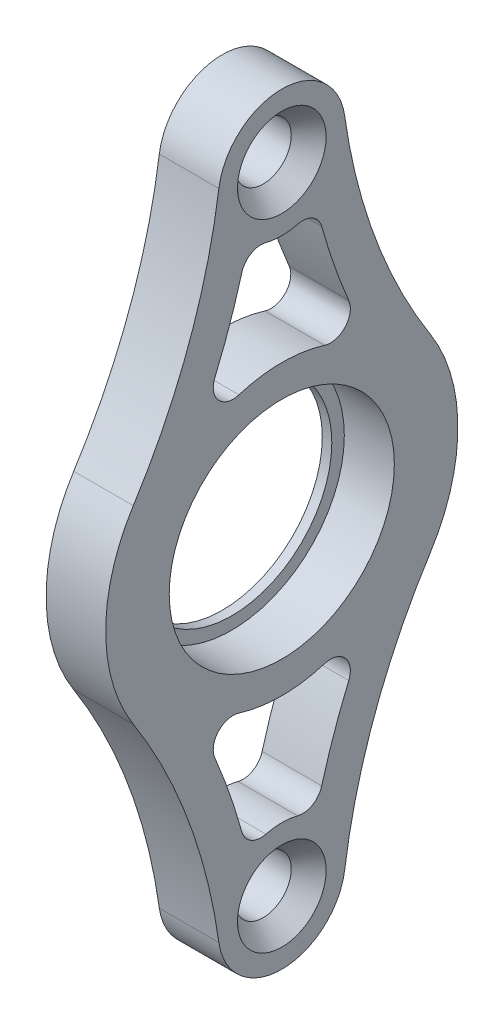
SolidWorks part; units mm, degrees
material "6061-T6 (SS)"
ref_plane "Front Plane" through (0, 0, 0) normal (0, 0, 1) x (1, 0, 0)
ref_plane "Top Plane" through (0, 0, 0) normal (0, 1, 0) x (1, 0, 0)
ref_plane "Right Plane" through (0, 0, 0) normal (1, 0, 0) x (0, 0, -1)
ref_plane "Plane1" through (56.0295, 0, 0) normal (-1, 0, 0) x (0, 0, 1)
sketch "Sketch1" plane through (56.0295, 0, 0) normal (-1, 0, 0) x (0, 0, 1)
  line L0 (-51.1134, 32.5835) -> (-5.0306, 26.107) construction
  line L1 (-23.0873, 0) -> (0, 0) construction
  line L2 (0, 0) -> (0, 25.4) construction
  circle A2 centre (0, -25.4) radius 2.2479
  circle A3 centre (0, 25.4) radius 2.2479
  circle A4 centre (0, 0) radius 9
  circle A5 centre (0, 0) radius 6 construction
  arc A6 (-11.8728, 7.5686) -> (-11.8728, -7.5686) centre (0, 0) ccw
  arc A7 (5.0306, 26.107) -> (-5.0306, 26.107) centre (0, 25.4) ccw
  arc A8 (-5.0306, -26.107) -> (5.0306, -26.107) centre (0, -25.4) ccw
  arc A9 (-5.0306, 26.107) -> (-11.8728, 7.5686) centre (-51.1134, 32.5835) cw
  arc A10 (5.0306, 26.107) -> (11.8728, 7.5686) centre (51.1134, 32.5835) ccw
  arc A11 (5.0306, -26.107) -> (11.8728, -7.5686) centre (51.1134, -32.5835) cw
  arc A12 (-5.0306, -26.107) -> (-11.8728, -7.5686) centre (-51.1134, -32.5835) ccw
  arc A13 (11.8728, -7.5686) -> (11.8728, 7.5686) centre (0, 0) ccw
  circle A14 centre (0, 25.4) radius 2.2479 construction
  circle A15 centre (0, -25.4) radius 2.2479 construction
  dimension "D1" = 18
  dimension "D2" = 12
  dimension "D4" = 10.16
  dimension "D3" = 5.08
  dimension "D5" = 8
extrude "Boss-Extrude1" add sketch "Sketch1" along normal blind 4.7625
sketch "Sketch2" plane through (51.267, 0, 0) normal (-1, 0, 0) x (0, 0, 1)
  arc A0 (-9.1955, 5.8619) -> (-1.8865, 25.6651) centre (-51.1134, 32.5835) ccw
  arc A1 (1.8865, 25.6651) -> (-1.8865, 25.6651) centre (0, 25.4) ccw
  arc A2 (1.8865, 25.6651) -> (9.1955, 5.8619) centre (51.1134, 32.5835) ccw
  arc A3 (9.1955, -5.8619) -> (9.1955, 5.8619) centre (0, 0) ccw
  arc A4 (9.1955, -5.8619) -> (1.8865, -25.6651) centre (51.1134, -32.5835) ccw
  arc A5 (-1.8865, -25.6651) -> (1.8865, -25.6651) centre (0, -25.4) ccw
  arc A6 (-1.8865, -25.6651) -> (-9.1955, -5.8619) centre (-51.1134, -32.5835) ccw
  arc A7 (-9.1955, 5.8619) -> (-9.1955, -5.8619) centre (0, 0) ccw
  arc A8 (-11.8728, 7.5686) -> (-5.0306, 26.107) centre (-51.1134, 32.5835) ccw
  arc A9 (-11.8728, 7.5686) -> (-11.8728, -7.5686) centre (0, 0) ccw
  arc A10 (-5.0306, -26.107) -> (-11.8728, -7.5686) centre (-51.1134, -32.5835) ccw
  arc A11 (-5.0306, -26.107) -> (5.0306, -26.107) centre (0, -25.4) ccw
  arc A12 (11.8728, -7.5686) -> (5.0306, -26.107) centre (51.1134, -32.5835) ccw
  arc A13 (11.8728, -7.5686) -> (11.8728, 7.5686) centre (0, 0) ccw
  arc A14 (5.0306, 26.107) -> (11.8728, 7.5686) centre (51.1134, 32.5835) ccw
  arc A15 (5.0306, 26.107) -> (-5.0306, 26.107) centre (0, 25.4) ccw
  arc A16 (-11.8728, 7.5686) -> (-5.0306, 26.107) centre (-51.1134, 32.5835) ccw construction
  arc A17 (-11.8728, 7.5686) -> (-11.8728, -7.5686) centre (0, 0) ccw construction
  arc A18 (-5.0306, -26.107) -> (-11.8728, -7.5686) centre (-51.1134, -32.5835) ccw construction
  arc A19 (-5.0306, -26.107) -> (5.0306, -26.107) centre (0, -25.4) ccw construction
  arc A20 (11.8728, -7.5686) -> (5.0306, -26.107) centre (51.1134, -32.5835) ccw construction
  arc A21 (11.8728, -7.5686) -> (11.8728, 7.5686) centre (0, 0) ccw construction
  arc A22 (5.0306, 26.107) -> (11.8728, 7.5686) centre (51.1134, 32.5835) ccw construction
  arc A23 (5.0306, 26.107) -> (-5.0306, 26.107) centre (0, 25.4) ccw construction
  circle A24 centre (0, 0) radius 11.54
  circle A25 centre (0, 25.4) radius 5.08
  circle A26 centre (0, -25.4) radius 5.08
  circle A27 centre (0, 0) radius 9 construction
  dimension "D3" = 2.54
  dimension "D1" = 0
  dimension "D2" = 3.175
extrude "Cut-Extrude1" cut sketch "Sketch2" against normal through all contours A25 A0 A24 A2 | A26 A4 A24 A6 region at (51.267, 15.0199, 0) region at (51.267, -15.0199, 0)
fillet "Fillet1" radius 1.5875 8 edges at (53.6483, 8.8063, 7.4579) (53.6483, 8.8063, -7.4579) (53.6483, 21.1234, 2.7417) (53.6483, -8.8063, -7.4579) (53.6483, -8.8063, 7.4579) (53.6483, -21.1234, 2.7417) (53.6483, -21.1234, -2.7417) (53.6483, 21.1234, -2.7417)
sketch "Sketch5" plane through (56.0295, 0, 0) normal (-1, 0, 0) x (0, 0, 1)
  point P0 (0, 25.4)
  point P3 (0, -25.4)
hole_wizard "CSK for #6 Flat Head Machine Screw1" positions "Sketch5" profile "Sketch4" countersink size "#6" standard "ANSI Inch"
sketch "Sketch4" plane through (56.0295, 25.4, 0) normal (0, 1, 0) x (0, 0, -1)
  line L0 (0, 0) -> (0, 7.6434)
  line L1 (0, 7.6434) -> (2.1526, 6.35)
  line L2 (2.1526, 6.35) -> (2.1526, 1.5998)
  line L3 (2.1526, 1.5998) -> (3.5433, 0)
  line L5 (3.5433, 0) -> (0, 0)
  line L6 (-2.1526, 1.5998) -> (-3.5433, 0) construction
  line L10 (0, 7.6434) -> (-2.1526, 6.35) construction
  line L11 (0, -6.35) -> (0, 107.95) construction
  dimension "Hole Dia." = 4.3053
  dimension "Hole Depth" = 6.35
  dimension "Near C'Sink Dia." = 7.0866
  dimension "Near C'Sink Angle" = 82
  dimension "Drill Angle" = 118
sketch "Sketch6" plane through (56.0295, 0, 0) normal (1, 0, 0) x (0, 0, -1)
  circle A0 centre (0, 0) radius 9 construction
  circle A1 centre (0, 0) radius 9
  circle A2 centre (0, 0) radius 8
  dimension "D1" = 1
extrude "Boss-Extrude2" add sketch "Sketch6" along normal offset from surface (0.7625 mm away) 4 from surface up to face at (56.0295, 25.4, -3.5433) starting at face at (51.267, -15.9859, 0)
equation "\"D1@Sketch1\"=18mm"
equation "\"D2@Sketch1\"=12mm"
equation "\"D1@Boss-Extrude2\"=4mm"
